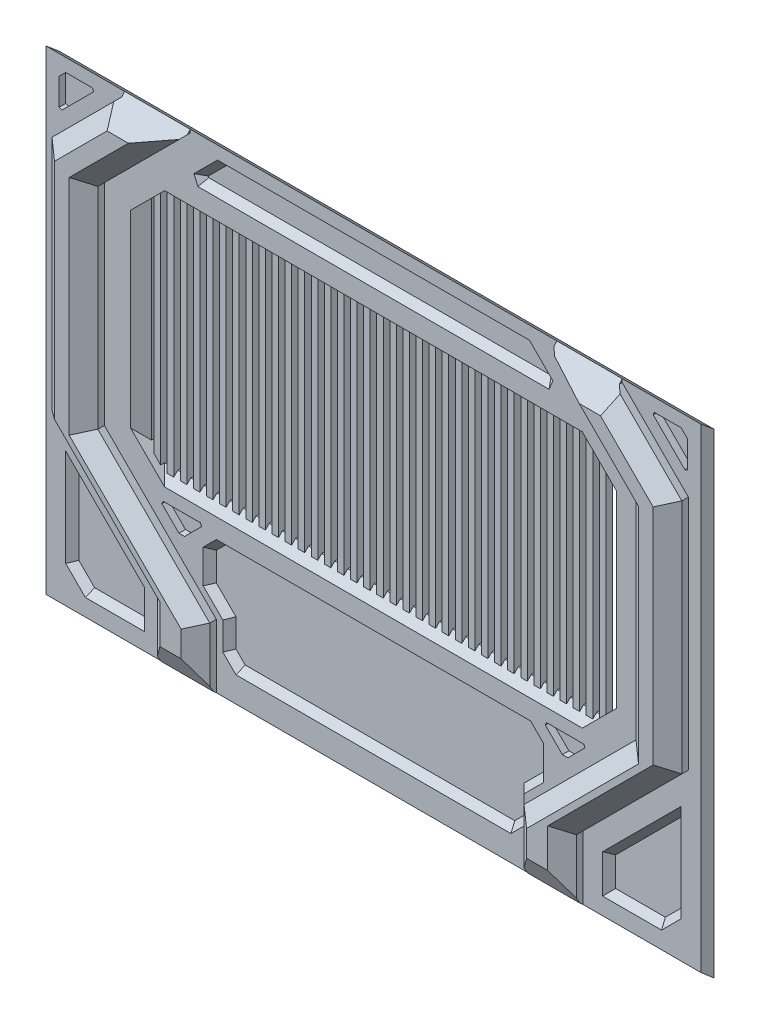
SolidWorks part; units mm, degrees
ref_plane "Plan de face" through (0, 0, 0) normal (0, 0, 1) x (1, 0, 0)
ref_plane "Plan de dessus" through (0, 0, 0) normal (0, 1, 0) x (1, 0, 0)
ref_plane "Plan de droite" through (0, 0, 0) normal (1, 0, 0) x (0, 0, -1)
sketch "Esquisse1" plane through (0, 0, 0) normal (0, 0, 1) x (1, 0, 0)
  line L1 (0, 0) -> (500, 0)
  line L2 (0, 0) -> (0, 385)
  line L3 (0, 385) -> (500, 385)
  line L4 (500, 0) -> (500, 385)
  dimension "D1" = 385
  dimension "D2" = 500
extrude "Boss.-Extru.1" add sketch "Esquisse1" along normal blind 10
sketch "Esquisse2" plane through (0, 0, 10) normal (0, 0, 1) x (1, 0, 0)
  line L1 (0, 0) -> (500, 0) construction
  line L3 (500, 385) -> (0, 385) construction
  line L4 (250, 385) -> (250, 0) construction
  line L6 (72.5, 315) -> (427.5, 315)
  line L7 (72.5, 315) -> (72.5, 135)
  line L8 (72.5, 135) -> (427.5, 135)
  line L9 (427.5, 315) -> (427.5, 135)
  point P10 (250, 315)
  dimension "D1" = 355
  dimension "D2" = 70
  dimension "D3" = 180
extrude "Enlèv. mat.-Extru.1" cut sketch "Esquisse2" against normal blind 5
sketch "Esquisse3" plane through (0, 0, 5) normal (0, 0, 1) x (1, 0, 0)
  line L0 (250, 315) -> (250, 135) construction
  line L1 (427.5, 315) -> (72.5, 315) construction
  line L2 (72.5, 135) -> (427.5, 135) construction
  line L3 (427.5, 315) -> (72.5, 315) construction
  line L4 (242.5, 315) -> (247.5, 315)
  line L5 (237.5, 315) -> (237.5, 135)
  line L6 (242.5, 315) -> (242.5, 135)
  line L7 (242.5, 135) -> (247.5, 135)
  line L8 (247.5, 315) -> (247.5, 135)
  line L9 (72.5, 135) -> (427.5, 135) construction
  line L10 (232.5, 315) -> (232.5, 135)
  line L11 (232.5, 135) -> (237.5, 135)
  line L12 (232.5, 315) -> (237.5, 315)
  line L13 (227.5, 315) -> (227.5, 135)
  line L14 (222.5, 315) -> (222.5, 135)
  line L15 (222.5, 135) -> (227.5, 135)
  line L16 (222.5, 315) -> (227.5, 315)
  line L17 (217.5, 315) -> (217.5, 135)
  line L18 (212.5, 315) -> (212.5, 135)
  line L19 (212.5, 135) -> (217.5, 135)
  line L20 (212.5, 315) -> (217.5, 315)
  line L21 (207.5, 315) -> (207.5, 135)
  line L22 (202.5, 315) -> (202.5, 135)
  line L23 (202.5, 135) -> (207.5, 135)
  line L24 (202.5, 315) -> (207.5, 315)
  line L25 (197.5, 315) -> (197.5, 135)
  line L26 (192.5, 315) -> (192.5, 135)
  line L27 (192.5, 135) -> (197.5, 135)
  line L28 (192.5, 315) -> (197.5, 315)
  line L29 (187.5, 315) -> (187.5, 135)
  line L30 (182.5, 315) -> (182.5, 135)
  line L31 (182.5, 135) -> (187.5, 135)
  line L32 (182.5, 315) -> (187.5, 315)
  line L33 (177.5, 315) -> (177.5, 135)
  line L34 (172.5, 315) -> (172.5, 135)
  line L35 (172.5, 135) -> (177.5, 135)
  line L36 (172.5, 315) -> (177.5, 315)
  line L37 (167.5, 315) -> (167.5, 135)
  line L38 (162.5, 315) -> (162.5, 135)
  line L39 (162.5, 135) -> (167.5, 135)
  line L40 (162.5, 315) -> (167.5, 315)
  line L41 (157.5, 315) -> (157.5, 135)
  line L42 (152.5, 315) -> (152.5, 135)
  line L43 (152.5, 135) -> (157.5, 135)
  line L44 (152.5, 315) -> (157.5, 315)
  line L45 (147.5, 315) -> (147.5, 135)
  line L46 (142.5, 315) -> (142.5, 135)
  line L47 (142.5, 135) -> (147.5, 135)
  line L48 (142.5, 315) -> (147.5, 315)
  line L49 (137.5, 315) -> (137.5, 135)
  line L50 (132.5, 315) -> (132.5, 135)
  line L51 (132.5, 135) -> (137.5, 135)
  line L52 (132.5, 315) -> (137.5, 315)
  line L53 (127.5, 315) -> (127.5, 135)
  line L54 (122.5, 315) -> (122.5, 135)
  line L55 (122.5, 135) -> (127.5, 135)
  line L56 (122.5, 315) -> (127.5, 315)
  line L57 (117.5, 315) -> (117.5, 135)
  line L58 (112.5, 315) -> (112.5, 135)
  line L59 (112.5, 135) -> (117.5, 135)
  line L60 (112.5, 315) -> (117.5, 315)
  line L61 (107.5, 315) -> (107.5, 135)
  line L62 (102.5, 315) -> (102.5, 135)
  line L63 (102.5, 135) -> (107.5, 135)
  line L64 (102.5, 315) -> (107.5, 315)
  line L65 (97.5, 315) -> (97.5, 135)
  line L66 (92.5, 315) -> (92.5, 135)
  line L67 (92.5, 135) -> (97.5, 135)
  line L68 (92.5, 315) -> (97.5, 315)
  line L69 (87.5, 315) -> (87.5, 135)
  line L70 (82.5, 315) -> (82.5, 135)
  line L71 (82.5, 135) -> (87.5, 135)
  line L72 (82.5, 315) -> (87.5, 315)
  line L73 (77.5, 315) -> (77.5, 135)
  line L74 (72.5, 315) -> (72.5, 135)
  line L75 (72.5, 135) -> (77.5, 135)
  line L76 (72.5, 315) -> (77.5, 315)
  line L77 (427.5, 315) -> (422.5, 315)
  line L78 (427.5, 135) -> (422.5, 135)
  line L79 (427.5, 315) -> (427.5, 135)
  line L80 (422.5, 315) -> (422.5, 135)
  line L81 (417.5, 315) -> (412.5, 315)
  line L82 (417.5, 135) -> (412.5, 135)
  line L83 (417.5, 315) -> (417.5, 135)
  line L84 (412.5, 315) -> (412.5, 135)
  line L85 (407.5, 315) -> (402.5, 315)
  line L86 (407.5, 135) -> (402.5, 135)
  line L87 (407.5, 315) -> (407.5, 135)
  line L88 (402.5, 315) -> (402.5, 135)
  line L89 (397.5, 315) -> (392.5, 315)
  line L90 (397.5, 135) -> (392.5, 135)
  line L91 (397.5, 315) -> (397.5, 135)
  line L92 (392.5, 315) -> (392.5, 135)
  line L93 (387.5, 315) -> (382.5, 315)
  line L94 (387.5, 135) -> (382.5, 135)
  line L95 (387.5, 315) -> (387.5, 135)
  line L96 (382.5, 315) -> (382.5, 135)
  line L97 (377.5, 315) -> (372.5, 315)
  line L98 (377.5, 135) -> (372.5, 135)
  line L99 (377.5, 315) -> (377.5, 135)
  line L100 (372.5, 315) -> (372.5, 135)
  line L101 (367.5, 315) -> (362.5, 315)
  line L102 (367.5, 135) -> (362.5, 135)
  line L103 (367.5, 315) -> (367.5, 135)
  line L104 (362.5, 315) -> (362.5, 135)
  line L105 (357.5, 315) -> (352.5, 315)
  line L106 (357.5, 135) -> (352.5, 135)
  line L107 (357.5, 315) -> (357.5, 135)
  line L108 (352.5, 315) -> (352.5, 135)
  line L109 (347.5, 315) -> (342.5, 315)
  line L110 (347.5, 135) -> (342.5, 135)
  line L111 (347.5, 315) -> (347.5, 135)
  line L112 (342.5, 315) -> (342.5, 135)
  line L113 (337.5, 315) -> (332.5, 315)
  line L114 (337.5, 135) -> (332.5, 135)
  line L115 (337.5, 315) -> (337.5, 135)
  line L116 (332.5, 315) -> (332.5, 135)
  line L117 (327.5, 315) -> (322.5, 315)
  line L118 (327.5, 135) -> (322.5, 135)
  line L119 (327.5, 315) -> (327.5, 135)
  line L120 (322.5, 315) -> (322.5, 135)
  line L121 (317.5, 315) -> (312.5, 315)
  line L122 (317.5, 135) -> (312.5, 135)
  line L123 (317.5, 315) -> (317.5, 135)
  line L124 (312.5, 315) -> (312.5, 135)
  line L125 (307.5, 315) -> (302.5, 315)
  line L126 (307.5, 135) -> (302.5, 135)
  line L127 (307.5, 315) -> (307.5, 135)
  line L128 (302.5, 315) -> (302.5, 135)
  line L129 (297.5, 315) -> (292.5, 315)
  line L130 (297.5, 135) -> (292.5, 135)
  line L131 (297.5, 315) -> (297.5, 135)
  line L132 (292.5, 315) -> (292.5, 135)
  line L133 (287.5, 315) -> (282.5, 315)
  line L134 (287.5, 135) -> (282.5, 135)
  line L135 (287.5, 315) -> (287.5, 135)
  line L136 (282.5, 315) -> (282.5, 135)
  line L137 (277.5, 315) -> (272.5, 315)
  line L138 (277.5, 135) -> (272.5, 135)
  line L139 (277.5, 315) -> (277.5, 135)
  line L140 (272.5, 315) -> (272.5, 135)
  line L141 (267.5, 315) -> (262.5, 315)
  line L142 (267.5, 135) -> (262.5, 135)
  line L143 (267.5, 315) -> (267.5, 135)
  line L144 (252.5, 315) -> (252.5, 135)
  line L145 (257.5, 135) -> (252.5, 135)
  line L146 (257.5, 315) -> (257.5, 135)
  line L147 (262.5, 315) -> (262.5, 135)
  line L148 (257.5, 315) -> (252.5, 315)
  dimension "D1" = 5
  dimension "D2" = 2.5
  dimension "D4" = 177.5
  dimension "D3" = 18
extrude "Enlèv. mat.-Extru.2" cut sketch "Esquisse3" against normal blind 5
chamfer "Chanfrein1" distance 10 angle 45 4 edges at (72.5, 135, 5) (427.5, 135, 5) (427.5, 315, 5) (72.5, 315, 5)
chamfer "Chanfrein4" distance 8 angle 45 4 edges at (427.5, 225, 10) (72.5, 225, 10) (250, 315, 10) (250, 135, 10)
sketch "Esquisse4" plane through (0, 0, 10) normal (0, 0, 1) x (1, 0, 0)
  line L0 (110, 385) -> (110, 370.7843)
  line L1 (500, 385) -> (0, 385) construction
  line L2 (110, 370.7843) -> (44.5, 305.2843)
  line L3 (44.5, 305.2843) -> (44.5, 144.7157)
  line L4 (44.5, 144.7157) -> (130, 59.2157)
  line L5 (130, 59.2157) -> (130, 0)
  line L6 (0, 0) -> (500, 0) construction
  line L7 (130, 0) -> (90, 0)
  line L8 (90, 0) -> (90, 59.2157)
  line L9 (90, 59.2157) -> (9.5, 139.7157)
  line L10 (64.5, 297) -> (90.5, 323) construction
  line L11 (9.5, 139.7157) -> (9.5, 320.2843)
  line L12 (9.5, 320.2843) -> (60, 370.7843)
  line L13 (60, 370.7843) -> (60, 385)
  line L14 (110, 370.7843) -> (60, 370.7843) construction
  line L15 (110, 385) -> (60, 385)
  line L16 (90.5, 127) -> (64.5, 153) construction
  line L17 (64.5, 153) -> (64.5, 297) construction
  line L18 (0, 385) -> (0, 0) construction
  line L19 (130, 59.2157) -> (90, 59.2157) construction
  line L20 (44.5, 305.2843) -> (9.5, 320.2843) construction
  line L21 (44.5, 144.7157) -> (9.5, 139.7157) construction
  line L22 (250, 0) -> (250, 385) construction
  line L23 (455.5, 144.7157) -> (490.5, 139.7157) construction
  line L24 (455.5, 305.2843) -> (490.5, 320.2843) construction
  line L25 (370, 59.2157) -> (410, 59.2157) construction
  line L26 (390, 370.7843) -> (440, 370.7843) construction
  line L27 (390, 385) -> (440, 385)
  line L28 (440, 370.7843) -> (440, 385)
  line L29 (490.5, 320.2843) -> (440, 370.7843)
  line L30 (490.5, 139.7157) -> (490.5, 320.2843)
  line L31 (410, 59.2157) -> (490.5, 139.7157)
  line L32 (410, 0) -> (410, 59.2157)
  line L33 (370, 0) -> (410, 0)
  line L34 (370, 59.2157) -> (370, 0)
  line L35 (455.5, 144.7157) -> (370, 59.2157)
  line L36 (455.5, 305.2843) -> (455.5, 144.7157)
  line L37 (390, 370.7843) -> (455.5, 305.2843)
  line L38 (390, 385) -> (390, 370.7843)
  dimension "D1" = 20
  dimension "D2" = 20
  dimension "D3" = 20
  dimension "D4" = 110
  dimension "D5" = 130
  dimension "D6" = 35
  dimension "D7" = 50
  dimension "D8" = 40
extrude "Boss.-Extru.2" add sketch "Esquisse4" along normal blind 15
chamfer "Chanfrein7" distance 10 angle 50 20 edges at (90, 29.6079, 25) (49.75, 99.4657, 25) (9.5, 230, 25) (34.75, 345.5343, 25) (60, 377.8921, 25) (390, 377.8921, 25) (422.75, 338.0343, 25) (455.5, 225, 25) (412.75, 101.9657, 25) (370, 29.6079, 25) (440, 377.8921, 25) (465.25, 345.5343, 25) (490.5, 230, 25) (450.25, 99.4657, 25) (410, 29.6079, 25) (110, 377.8921, 25) (77.25, 338.0343, 25) (44.5, 225, 25) (87.25, 101.9657, 25) (130, 29.6079, 25) first distance on face at (90, 37.0098, 19.375) first distance on face at (49.75, 99.4657, 17.5) first distance on face at (9.5, 230, 17.5) first distance on face at (34.75, 345.5343, 17.5) first distance on face at (60, 379.6691, 19.375) first distance on face at (390, 377.8921, 17.5) first distance on face at (422.75, 338.0343, 17.5) first distance on face at (455.5, 225, 17.5) first distance on face at (412.75, 101.9657, 17.5) first distance on face at (370, 29.6079, 17.5) first distance on face at (440, 377.8921, 17.5) first distance on face at (465.25, 345.5343, 17.5) first distance on face at (490.5, 230, 17.5) first distance on face at (450.25, 99.4657, 17.5) first distance on face at (410, 29.6079, 17.5) first distance on face at (110, 376.1152, 19.375) first distance on face at (77.25, 338.0343, 17.5) first distance on face at (44.5, 225, 17.5) first distance on face at (87.25, 101.9657, 17.5) first distance on face at (130, 22.2059, 19.375)
chamfer "Chanfrein5" distance 20 angle 60 1 edges at (110, 0, 25) first distance on face at (236.875, 0, 14.0625)
chamfer "Chanfrein8" distance 20 angle 50 1 edges at (250, 385, 0) first distance on face at (255, 225, 0)
sketch "Esquisse5" plane through (0, 0, 10) normal (0, 0, 1) x (1, 0, 0)
  line L0 (250, 127) -> (250, 8.6603) construction
  line L1 (409.5, 127) -> (90.5, 127) construction
  line L2 (130, 8.6603) -> (370, 8.6603) construction
  line L3 (370, 112) -> (130, 112)
  line L4 (120, 102) -> (120, 76.2868)
  line L5 (145, 30) -> (355, 30)
  line L6 (500, 0) -> (0, 0) construction
  line L7 (120, 76.2868) -> (135, 61.2868)
  line L8 (130, 112) -> (120, 102)
  line L9 (105.7292, 101.8713) -> (118.7365, 114.8787)
  line L10 (117.8579, 117) -> (89.3579, 117)
  line L11 (88.4792, 114.8787) -> (101.4865, 101.8713)
  line L12 (130, 59.2157) -> (44.5, 144.7157) construction
  line L13 (44.5, 144.7157) -> (130, 59.2157) construction
  line L14 (89.3579, 117) -> (88.4792, 114.8787)
  line L15 (118.7365, 114.8787) -> (117.8579, 117)
  line L16 (101.4865, 101.8713) -> (105.7292, 101.8713)
  line L17 (250, 127) -> (250, 373.391) construction
  line L18 (390, 373.391) -> (110, 373.391) construction
  line L19 (369.109, 363.391) -> (130.891, 363.391)
  line L20 (130.891, 363.391) -> (112.9621, 345.4621)
  line L21 (115.891, 338.391) -> (384.109, 338.391)
  line L22 (64.5, 297) -> (90.5, 323) construction
  line L23 (105.891, 338.391) -> (90.5, 323) construction
  line L24 (112.9621, 345.4621) -> (115.891, 338.391)
  line L25 (75, 23.6603) -> (75, 53.0025)
  line L26 (75, 53.0025) -> (15, 113.0025)
  line L27 (15, 113.0025) -> (15, 38.6603)
  line L28 (15, 38.6603) -> (30, 23.6603)
  line L29 (30, 23.6603) -> (75, 23.6603)
  line L30 (90, 59.2157) -> (9.5, 139.7157) construction
  line L31 (0, 8.6603) -> (90, 8.6603) construction
  line L32 (90, 17.3205) -> (90, 59.2157) construction
  line L33 (0, 373.391) -> (0, 8.6603) construction
  line L34 (30, 23.6603) -> (30, 38.6603) construction
  line L35 (30, 38.6603) -> (15, 38.6603) construction
  line L36 (12.1213, 337.0477) -> (36.3433, 361.2697)
  line L37 (35.4646, 363.391) -> (15, 363.391)
  line L38 (15, 363.391) -> (10, 358.391)
  line L39 (10, 358.391) -> (10, 337.9264)
  line L40 (130.891, 363.391) -> (38.4646, 363.391) construction
  line L41 (60, 370.7843) -> (9.5, 320.2843) construction
  line L42 (9.5, 320.2843) -> (60, 370.7843) construction
  line L43 (15, 363.391) -> (10, 363.391) construction
  line L44 (10, 363.391) -> (10, 358.391) construction
  line L45 (10, 337.9264) -> (12.1213, 337.0477)
  line L46 (36.3433, 361.2697) -> (35.4646, 363.391)
  line L47 (490, 363.391) -> (490, 358.391) construction
  line L48 (485, 363.391) -> (490, 363.391) construction
  line L49 (369.109, 363.391) -> (461.5354, 363.391) construction
  line L50 (470, 38.6603) -> (485, 38.6603) construction
  line L51 (470, 23.6603) -> (470, 38.6603) construction
  line L52 (394.109, 338.391) -> (409.5, 323) construction
  line L53 (463.6567, 361.2697) -> (464.5354, 363.391)
  line L54 (490, 337.9264) -> (487.8787, 337.0477)
  line L55 (490, 358.391) -> (490, 337.9264)
  line L56 (485, 363.391) -> (490, 358.391)
  line L57 (464.5354, 363.391) -> (485, 363.391)
  line L58 (487.8787, 337.0477) -> (463.6567, 361.2697)
  line L59 (470, 23.6603) -> (425, 23.6603)
  line L60 (485, 38.6603) -> (470, 23.6603)
  line L61 (485, 113.0025) -> (485, 38.6603)
  line L62 (425, 53.0025) -> (485, 113.0025)
  line L63 (425, 23.6603) -> (425, 53.0025)
  line L64 (387.0379, 345.4621) -> (384.109, 338.391)
  line L65 (369.109, 363.391) -> (387.0379, 345.4621)
  line L66 (398.5135, 101.8713) -> (394.2708, 101.8713)
  line L67 (381.2635, 114.8787) -> (382.1421, 117)
  line L68 (410.6421, 117) -> (411.5208, 114.8787)
  line L69 (411.5208, 114.8787) -> (398.5135, 101.8713)
  line L70 (382.1421, 117) -> (410.6421, 117)
  line L71 (394.2708, 101.8713) -> (381.2635, 114.8787)
  line L72 (370, 112) -> (380, 102)
  line L73 (130, 8.6603) -> (130, 59.2157) construction
  line L74 (380, 102) -> (380, 76.2868)
  line L75 (135, 61.2868) -> (135, 40)
  line L76 (135, 40) -> (145, 30)
  line L77 (380, 76.2868) -> (365, 61.2868)
  line L78 (120, 76.2868) -> (120, 30) construction
  line L79 (145, 30) -> (120, 30) construction
  line L80 (365, 61.2868) -> (365, 40)
  line L81 (365, 40) -> (355, 30)
  point P6 (490, 334.9264)
  point P7 (120, 112)
  point P9 (120, 30)
  point P10 (250, 112)
  point P16 (103.6079, 99.75)
  point P17 (120.8579, 117)
  point P19 (86.3579, 117)
  point P36 (250, 363.391)
  point P55 (10, 334.9264)
  point P88 (250, 338.391)
  point P98 (250, 30)
  point P99 (413.6421, 117)
  point P100 (379.1421, 117)
  point P101 (396.3921, 99.75)
  point P102 (380, 30)
  point P103 (380, 112)
  dimension "D1" = 30
  dimension "D2" = 15
  dimension "D3" = 130
  dimension "D23" = 5
  dimension "D6" = 5
  dimension "D4" = 10
  dimension "D5" = 10
  dimension "D8" = 10
  dimension "D9" = 10
  dimension "D10" = 25
  dimension "D11" = 15
  dimension "D15" = 15
  dimension "D16" = 15
  dimension "D18" = 15
  dimension "D19" = 15
  dimension "D20" = 10
  dimension "D21" = 10
  dimension "D22" = 5
  dimension "D24" = 10
extrude "Enlèv. mat.-Extru.4" cut sketch "Esquisse5" against normal blind 5
chamfer "Chanfrein9" distance 5 angle 45 28 edges at (250, 363.391, 5) (378.0735, 354.4265, 5) (385.5735, 341.9265, 5) (250, 338.391, 5) (114.4265, 341.9265, 5) (121.9265, 354.4265, 5) (22.5, 31.1603, 5) (15, 75.8314, 5) (45, 83.0025, 5) (52.5, 23.6603, 5) (477.5, 31.1603, 5) (447.5, 23.6603, 5) (455, 83.0025, 5) (485, 75.8314, 5) (120, 89.1434, 5) (125, 107, 5) (250, 112, 5) (375, 107, 5) (380, 89.1434, 5) (250, 30, 5) (127.5, 68.7868, 5) (75, 38.3314, 5) (425, 38.3314, 5) (360, 35, 5) (140, 35, 5) (135, 50.6434, 5) (372.5, 68.7868, 5) (365, 50.6434, 5)
sketch "Esquisse6" plane through (0, 214.1908, -179.7274) normal (0, 0.766, -0.6428) x (1, 0, 0)
  line L0 (60, -247.6716) -> (0, -247.6716) construction
  line L1 (48.2433, -247.6716) -> (454.0112, -247.6716)
  line L2 (48.2433, -247.6716) -> (48.2433, -286.582)
  line L3 (48.2433, -286.582) -> (454.0112, -286.582)
  line L4 (454.0112, -247.6716) -> (454.0112, -286.582)
extrude "Enlèv. mat.-Extru.5" cut sketch "Esquisse6" against normal through all
ref_plane "Plan1" through (0, 0, 0) normal (0, 0.7559, -0.6547) x (1, 0, 0)
sketch "Esquisse7" plane through (0, 0, 0) normal (0, 0.7559, -0.6547) x (1, 0, 0)
  line L1 (0, 0) -> (500, 0)
  line L2 (0, 0) -> (0, -13.2288)
  line L3 (0, -13.2288) -> (500, -13.2288)
  line L4 (500, 0) -> (500, -13.2288)
extrude "Enlèv. mat.-Extru.6" cut sketch "Esquisse7" against normal blind 10
sketch "Esquisse8" plane through (0, 0, 0) normal (0, -0.7559, 0.6547) x (-1, 0, 0)
  line L1 (0, 0) -> (-564.967, 0)
  line L2 (0, 0) -> (0, -36.5205)
  line L3 (0, -36.5205) -> (-564.967, -36.5205)
  line L4 (-564.967, 0) -> (-564.967, -36.5205)
extrude "Enlèv. mat.-Extru.7" cut sketch "Esquisse8" against normal blind 1.5
